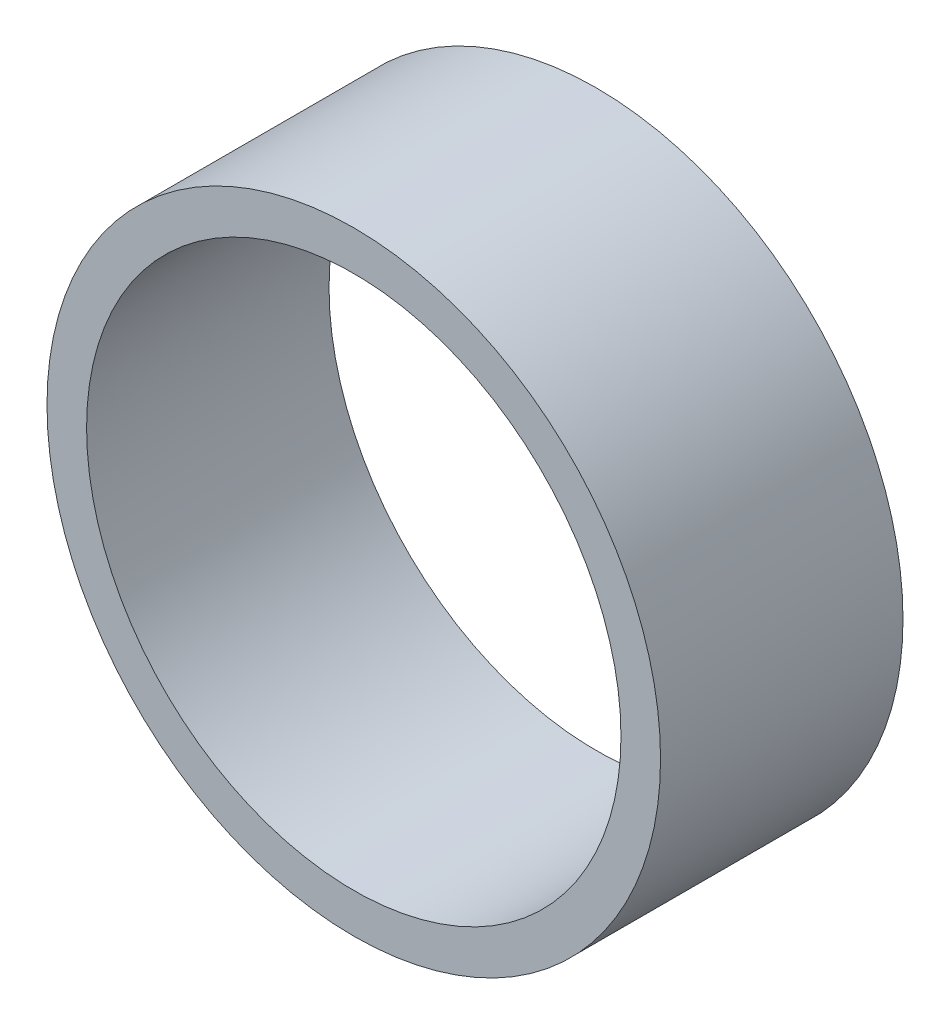
SolidWorks part; units mm, degrees
ref_plane "Front" through (0, 0, 0) normal (0, 0, 1) x (1, 0, 0)
ref_plane "Top" through (0, 0, 0) normal (0, 1, 0) x (1, 0, 0)
ref_plane "Right" through (0, 0, 0) normal (1, 0, 0) x (0, 0, -1)
sketch "Esquisse1" plane through (0, 0, 0) normal (0, 0, 1) x (1, 0, 0)
  circle A0 centre (0, 0) radius 27
  circle A1 centre (0, 0) radius 31
  dimension "D1" = 54
  dimension "D2" = 62
extrude "Boss.-Extru.1" add sketch "Esquisse1" along normal blind 24.5
